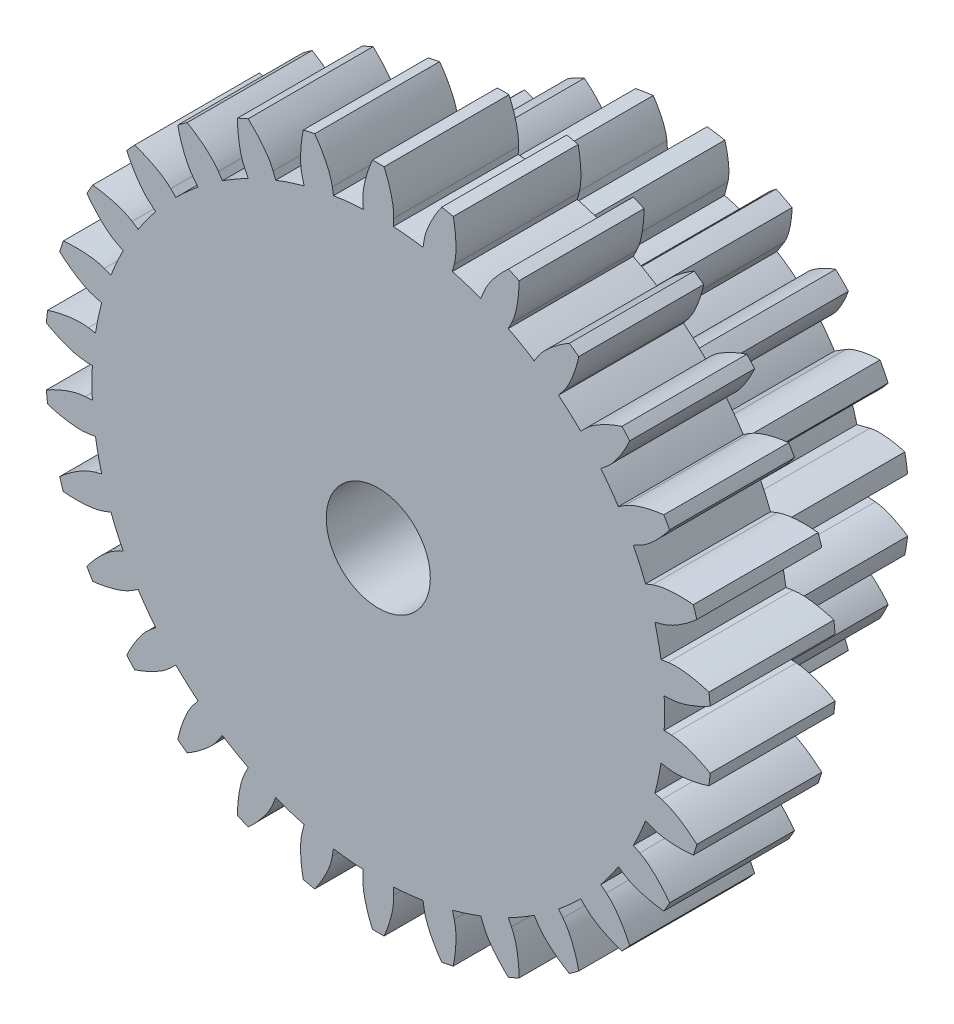
SolidWorks part; units mm, degrees
ref_plane "前视基准面" through (0, 0, 0) normal (0, 0, 1) x (1, 0, 0)
ref_plane "上视基准面" through (0, 0, 0) normal (0, 1, 0) x (1, 0, 0)
ref_plane "右视基准面" through (0, 0, 0) normal (1, 0, 0) x (0, 0, -1)
other "Configuration Table"
sketch "草图1" plane through (0, 0, 0) normal (0, 0, 1) x (1, 0, 0)
  line L0 (0, 0) -> (2, 0) construction
  line L1 (0, 0) -> (1.9938, 0.1569) construction
  line L2 (0, 0) -> (1.875, 0.1277)
  line L3 (1.9938, 0.1569) -> (1.9938, -0.1569) construction
  line L4 (0, 0) -> (1.875, -0.1277)
  circle A0 centre (0, 0) radius 2.2
  circle A1 centre (0, 0) radius 2 construction
  circle A2 centre (0, 0) radius 1.75
  circle A3 centre (0, 0) radius 1.8794 construction
  circle A4 centre (0, 0) radius 0.5
  spline S0 degree 4 poles (1.875, 0.1277) (1.8893, 0.1287) (1.929, 0.1344) (2.0025, 0.157) (2.1154, 0.2097) (2.2496, 0.2999) (2.4038, 0.439) (2.558, 0.6275) (2.6959, 0.8566) (2.809, 1.1216) (2.8885, 1.3983) (2.9362, 1.6822) (2.9548, 1.9837) (2.9388, 2.3574) (2.8628, 2.7975) (2.7005, 3.2908) (2.438, 3.8043) (2.1043, 4.2744) (1.7108, 4.6951) (1.2662, 5.062) (0.7817, 5.3723) (0.2626, 5.6242) (-0.2099, 5.7928) (-0.6312, 5.9005) (-0.9788, 5.9657) (-1.275, 6.0034) (-1.5146, 6.0246) (-1.7994, 6.0339) (-1.9848, 6.0333) (-2.2485, 6.0248) (-2.4456, 6.0069) (-2.6444, 5.9868) (-2.7432, 5.9706) (-2.8075, 5.9617) knots 0 0 0 0 0 0.005604 0.015718 0.02996 0.048734 0.068727 0.096889 0.125051 0.153212 0.181374 0.209535 0.237696 0.271429 0.327752 0.384075 0.440398 0.496721 0.553044 0.609367 0.66569 0.722013 0.778336 0.806497 0.834659 0.86282 0.890982 0.909091 0.931818 0.954545 0.977273 1 1 1 1 1 construction
  spline S1 degree 4 poles (1.875, 0.1277) (1.8893, 0.1287) (1.929, 0.1344) (2.0025, 0.157) (2.1154, 0.2097) (2.2496, 0.2999) (2.4038, 0.439) (2.558, 0.6275) (2.6959, 0.8566) (2.809, 1.1216) (2.8885, 1.3983) (2.9362, 1.6822) (2.9548, 1.9837) (2.9388, 2.3574) (2.8628, 2.7975) (2.7005, 3.2908) (2.438, 3.8043) (2.1043, 4.2744) (1.7108, 4.6951) (1.2662, 5.062) (0.7817, 5.3723) (0.2626, 5.6242) (-0.2099, 5.7928) (-0.6312, 5.9005) (-0.9788, 5.9657) (-1.275, 6.0034) (-1.5146, 6.0246) (-1.7328, 6.0317) (-1.8402, 6.033) (-1.8822, 6.033) knots 0 0 0 0 0 0.005604 0.015718 0.02996 0.048734 0.068727 0.096889 0.125051 0.153212 0.181374 0.209535 0.237696 0.271429 0.327752 0.384075 0.440398 0.496721 0.553044 0.609367 0.66569 0.722013 0.778336 0.806497 0.834659 0.86282 0.890982 0.909091 0.909091 0.909091 0.909091 0.909091
  spline S2 degree 4 poles (1.875, -0.1277) (1.8893, -0.1287) (1.929, -0.1344) (2.0025, -0.157) (2.1154, -0.2097) (2.2496, -0.2999) (2.4038, -0.439) (2.558, -0.6275) (2.6959, -0.8566) (2.809, -1.1216) (2.8885, -1.3983) (2.9362, -1.6822) (2.9548, -1.9837) (2.9388, -2.3574) (2.8628, -2.7975) (2.7005, -3.2908) (2.438, -3.8043) (2.1043, -4.2744) (1.7108, -4.6951) (1.2662, -5.062) (0.7817, -5.3723) (0.2626, -5.6242) (-0.2099, -5.7928) (-0.6312, -5.9005) (-0.9788, -5.9657) (-1.275, -6.0034) (-1.5146, -6.0246) (-1.7994, -6.0339) (-1.9848, -6.0333) (-2.2485, -6.0248) (-2.4456, -6.0069) (-2.6444, -5.9868) (-2.7432, -5.9706) (-2.8075, -5.9617) knots 0 0 0 0 0 0.005604 0.015718 0.02996 0.048734 0.068727 0.096889 0.125051 0.153212 0.181374 0.209535 0.237696 0.271429 0.327752 0.384075 0.440398 0.496721 0.553044 0.609367 0.66569 0.722013 0.778336 0.806497 0.834659 0.86282 0.890982 0.909091 0.931818 0.954545 0.977273 1 1 1 1 1 construction
  spline S3 degree 4 poles (1.875, -0.1277) (1.8893, -0.1287) (1.929, -0.1344) (2.0025, -0.157) (2.1154, -0.2097) (2.2496, -0.2999) (2.4038, -0.439) (2.558, -0.6275) (2.6959, -0.8566) (2.809, -1.1216) (2.8885, -1.3983) (2.9362, -1.6822) (2.9548, -1.9837) (2.9388, -2.3574) (2.8628, -2.7975) (2.7005, -3.2908) (2.438, -3.8043) (2.1043, -4.2744) (1.7108, -4.6951) (1.2662, -5.062) (0.7817, -5.3723) (0.2626, -5.6242) (-0.2099, -5.7928) (-0.6312, -5.9005) (-0.9788, -5.9657) (-1.275, -6.0034) (-1.5146, -6.0246) (-1.7328, -6.0317) (-1.8402, -6.033) (-1.8822, -6.033) knots 0 0 0 0 0 0.005604 0.015718 0.02996 0.048734 0.068727 0.096889 0.125051 0.153212 0.181374 0.209535 0.237696 0.271429 0.327752 0.384075 0.440398 0.496721 0.553044 0.609367 0.66569 0.722013 0.778336 0.806497 0.834659 0.86282 0.890982 0.909091 0.909091 0.909091 0.909091 0.909091
  point P15 (1.9938, 0)
  dimension "齿顶圆直径" = 4.4
  dimension "分度圆直径" = 4
  dimension "齿根圆直径" = 3.5
  dimension "基圆直径" = 3.7588
  dimension "内孔直径" = 1
  dimension "渐近线镜像线夹角" = 4.5
extrude "凸台-拉伸1" add sketch "草图1" along normal blind 1.7 contours A0 | A4
extrude "切除-拉伸1" cut sketch "草图1<3>" along normal through all contours A2 S3 A0 S1 region at (2.0041, 0, 0)
sketch "草图1<3>" plane through (0, 0, 0) normal (0, 0, 1) x (1, 0, 0) same geometry as "草图1"
pattern_circular "阵列(圆周)1" count 20 every 18 about axis through (0, 0, 1.7) along (0, 0, 1) of "切除-拉伸1"
sketch "草图2" plane through (0, 0, 1.7) normal (0, 0, 1) x (1, 0, 0)
  line L0 (0, 0) -> (3, 0) construction
  line L1 (0, 0) -> (2.8152, 0.1475)
  line L2 (0, 0) -> (2.8152, -0.1475)
  line L3 (2.8152, 0.1475) -> (2.8152, -0.1475) construction
  circle A0 centre (0, 0) radius 3 construction
  circle A1 centre (0, 0) radius 2.8191 construction
  circle A2 centre (0, 0) radius 2.75
  circle A3 centre (0, 0) radius 3.2
  circle A4 centre (0, 0) radius 0.5
  spline S0 degree 4 poles (2.8152, -0.1475) (2.8367, -0.1487) (2.8963, -0.1563) (3.0071, -0.1885) (3.1777, -0.2648) (3.3811, -0.397) (3.6155, -0.602) (3.8513, -0.881) (4.0635, -1.2213) (4.2394, -1.6162) (4.365, -2.0294) (4.4433, -2.4541) (4.4782, -2.9057) (4.4631, -3.4665) (4.3592, -4.1285) (4.1278, -4.8721) (3.7457, -5.6484) (3.257, -6.3614) (2.6755, -7.0016) (2.0192, -7.5623) (1.2967, -8.0391) (0.5293, -8.429) (-0.2857, -8.7309) (-1.0078, -8.9177) (-1.6623, -9.0235) (-2.1343, -9.0715) (-2.5561, -9.092) (-2.8357, -9.0955) (-3.23, -9.0889) (-3.5275, -9.0667) (-3.825, -9.0413) (-3.9743, -9.0192) (-4.0706, -9.0075) knots 0 0 0 0 0 0.005604 0.015718 0.02996 0.048734 0.068727 0.096889 0.125051 0.153212 0.181374 0.209535 0.237696 0.271429 0.327752 0.384075 0.440398 0.496721 0.553044 0.609367 0.66569 0.722013 0.778336 0.834659 0.86282 0.890982 0.909091 0.931818 0.954545 0.977273 1 1 1 1 1 construction
  spline S1 degree 4 poles (2.8152, -0.1475) (2.8367, -0.1487) (2.8963, -0.1563) (3.0071, -0.1885) (3.1777, -0.2648) (3.3811, -0.397) (3.6155, -0.602) (3.8513, -0.881) (4.0635, -1.2213) (4.2394, -1.6162) (4.365, -2.0294) (4.4433, -2.4541) (4.4782, -2.9057) (4.4631, -3.4665) (4.3592, -4.1285) (4.1278, -4.8721) (3.7457, -5.6484) (3.257, -6.3614) (2.6755, -7.0016) (2.0192, -7.5623) (1.2967, -8.0391) (0.5293, -8.429) (-0.2857, -8.7309) (-1.0078, -8.9177) (-1.6623, -9.0235) (-2.1343, -9.0715) (-2.4574, -9.0872) (-2.6182, -9.0916) (-2.6811, -9.0926) knots 0 0 0 0 0 0.005604 0.015718 0.02996 0.048734 0.068727 0.096889 0.125051 0.153212 0.181374 0.209535 0.237696 0.271429 0.327752 0.384075 0.440398 0.496721 0.553044 0.609367 0.66569 0.722013 0.778336 0.834659 0.86282 0.890982 0.909091 0.909091 0.909091 0.909091 0.909091
  spline S2 degree 4 poles (2.8152, 0.1475) (2.8367, 0.1487) (2.8963, 0.1563) (3.0071, 0.1885) (3.1777, 0.2648) (3.3811, 0.397) (3.6155, 0.602) (3.8513, 0.881) (4.0635, 1.2213) (4.2394, 1.6162) (4.365, 2.0294) (4.4433, 2.4541) (4.4782, 2.9057) (4.4631, 3.4665) (4.3592, 4.1285) (4.1278, 4.8721) (3.7457, 5.6484) (3.257, 6.3614) (2.6755, 7.0016) (2.0192, 7.5623) (1.2967, 8.0391) (0.5293, 8.429) (-0.2857, 8.7309) (-1.0078, 8.9177) (-1.6623, 9.0235) (-2.1343, 9.0715) (-2.5561, 9.092) (-2.8357, 9.0955) (-3.23, 9.0889) (-3.5275, 9.0667) (-3.825, 9.0413) (-3.9743, 9.0192) (-4.0706, 9.0075) knots 0 0 0 0 0 0.005604 0.015718 0.02996 0.048734 0.068727 0.096889 0.125051 0.153212 0.181374 0.209535 0.237696 0.271429 0.327752 0.384075 0.440398 0.496721 0.553044 0.609367 0.66569 0.722013 0.778336 0.834659 0.86282 0.890982 0.909091 0.931818 0.954545 0.977273 1 1 1 1 1 construction
  spline S3 degree 4 poles (2.8152, 0.1475) (2.8367, 0.1487) (2.8963, 0.1563) (3.0071, 0.1885) (3.1777, 0.2648) (3.3811, 0.397) (3.6155, 0.602) (3.8513, 0.881) (4.0635, 1.2213) (4.2394, 1.6162) (4.365, 2.0294) (4.4433, 2.4541) (4.4782, 2.9057) (4.4631, 3.4665) (4.3592, 4.1285) (4.1278, 4.8721) (3.7457, 5.6484) (3.257, 6.3614) (2.6755, 7.0016) (2.0192, 7.5623) (1.2967, 8.0391) (0.5293, 8.429) (-0.2857, 8.7309) (-1.0078, 8.9177) (-1.6623, 9.0235) (-2.1343, 9.0715) (-2.4574, 9.0872) (-2.6182, 9.0916) (-2.6811, 9.0926) knots 0 0 0 0 0 0.005604 0.015718 0.02996 0.048734 0.068727 0.096889 0.125051 0.153212 0.181374 0.209535 0.237696 0.271429 0.327752 0.384075 0.440398 0.496721 0.553044 0.609367 0.66569 0.722013 0.778336 0.834659 0.86282 0.890982 0.909091 0.909091 0.909091 0.909091 0.909091
  point P16 (2.8152, 0)
  dimension "内孔直径" = 1
  dimension "分度圆直径" = 6
  dimension "齿顶圆直径" = 6.4
  dimension "基圆直径" = 5.6382
  dimension "齿根圆直径" = 5.5
  dimension "渐开线镜像线夹角" = 3
extrude "凸台-拉伸2" add sketch "草图2" along normal blind 1.2 contours A3 | A4
extrude "切除-拉伸3" cut sketch "草图2<3>" along normal through all contours S3 L1 A2 L2 S1 A3 region at (2.9999, 0, 1.7)
sketch "草图2<3>" plane through (0, 0, 1.7) normal (0, 0, 1) x (1, 0, 0) same geometry as "草图2"
pattern_circular "阵列(圆周)2" count 30 over 360 about axis through (0, 0, 2.9) along (0, 0, 1) of "切除-拉伸3"
equation "\"m\"= 0.2'模数"
equation "\"z\" = 20'齿数"
equation "\"a\"= 20度'压力角"
equation "\"d\"= \"m\" * \"z\"'分度圆直径"
equation "\"da\"= ( \"z\" + 2 ) * \"m\"'齿顶圆直径"
equation "\"df\"= ( \"z\" - 2.5 ) * \"m\"'齿根圆直径"
equation "\"s\"= 0.5 * PI * \"m\"'分度圆齿厚"
equation "\"r\"= 0.38 * \"m\"'齿根圆角"
equation "\"B\"= 0.3 * \"d\"'齿厚"
equation "\"db\"= \"m\" * \"z\" * cos ( \"a\" )'基圆直径"
equation "\"rb\"= \"db\" / 2'基圆半径"
equation "\"齿顶圆直径@草图1\"= \"da\""
equation "\"分度圆直径@草图1\"= \"d\""
equation "\"齿根圆直径@草图1\"= \"df\""
equation "\"基圆直径@草图1\"= \"db\""
equation "\"渐近线镜像线夹角@草图1\"= 360 / 4 / \"z\""
equation "\"h\" = 1.7mm'齿轮厚度"
equation "\"ir\"= 1mm'内孔直径"
equation "\"内孔直径@草图1\"= \"ir\""
equation "\"齿轮厚@凸台-拉伸1\"= \"h\""
equation "\"齿轮夹角@阵列(圆周)1\"= 360 / \"z\""
equation "\"齿数@阵列(圆周)1\"= \"z\""
equation "\"m1\"= 0.2'模数"
equation "\"z1\" = 30'齿数"
equation "\"a1\"= 20度'压力角"
equation "\"d1\"= \"m1\" * \"z1\"'分度圆直径"
equation "\"da1\"= ( \"z1\" + 2 ) * \"m1\"'齿顶圆直径"
equation "\"df1\"= ( \"z1\" - 2.5 ) * \"m1\"'齿根圆直径"
equation "\"s1\"= 0.5 * PI * \"m1\"'分度圆齿厚"
equation "\"r1\"= 0.38 * \"m1\"'齿根圆角"
equation "\"B1\"= 0.3 * \"d1\"'齿厚"
equation "\"db1\"= \"m1\" * \"z1\" * cos ( \"a1\" )'基圆直径"
equation "\"rb1\"= \"db1\" / 2'基圆半径"
equation "\"分度圆直径@草图2\"= \"d1\""
equation "\"齿顶圆直径@草图2\"= \"da1\""
equation "\"基圆直径@草图2\"= \"db1\""
equation "\"齿根圆直径@草图2\"= \"df1\""
equation "\"渐开线镜像线夹角@草图2\"= 360 / 4 / \"z1\""
equation "\"内孔直径@草图2\"= \"ir\""
equation "\"二层齿轮厚@凸台-拉伸2\" = \"h1\""
equation "\"h1\" = 1.2'齿轮厚度"
equation "\"二层齿数@阵列(圆周)2\"= \"z1\""
